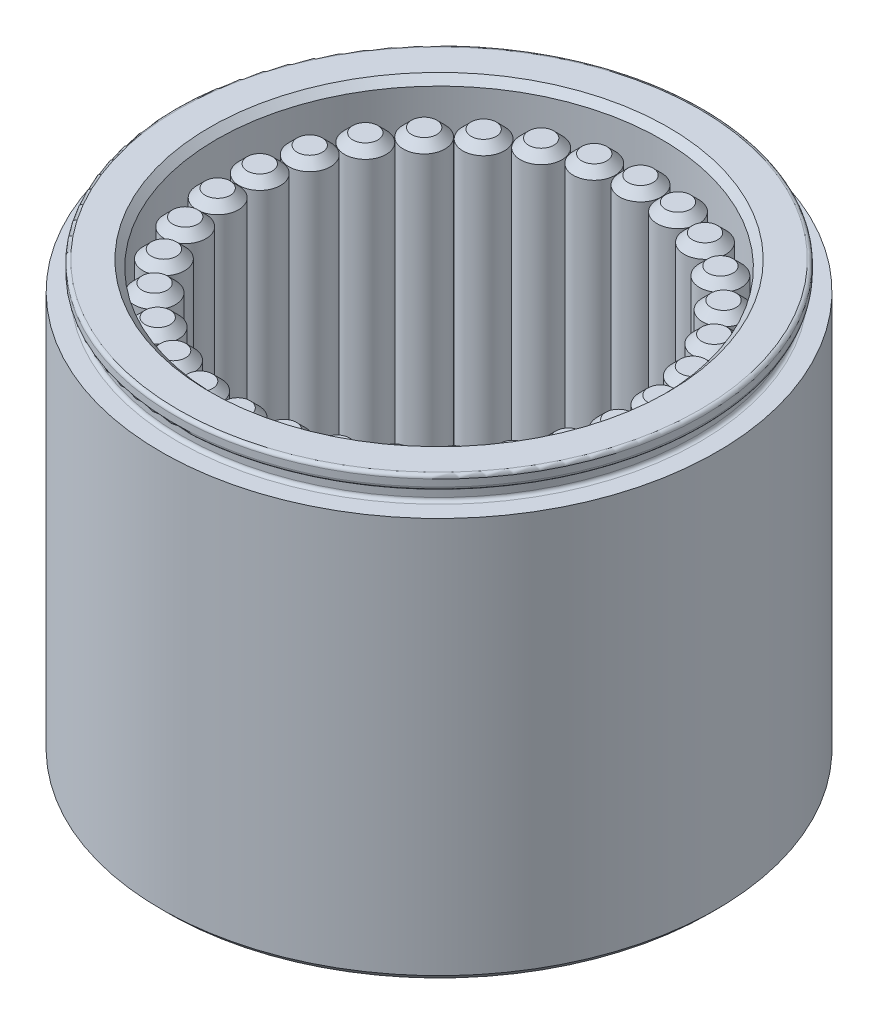
SolidWorks part; units mm, degrees
material "ASTM A36 Acero"
ref_plane "Alzado" through (0, 0, 0) normal (0, 0, 1) x (1, 0, 0)
ref_plane "Planta" through (0, 0, 0) normal (0, 1, 0) x (1, 0, 0)
ref_plane "Vista lateral" through (0, 0, 0) normal (1, 0, 0) x (0, 0, -1)
sketch "Croquis1" plane through (0, 0, 0) normal (0, 0, 1) x (1, 0, 0)
  line L0 (0, 0) -> (20, 0)
  line L1 (20, 0) -> (20, 29)
  line L2 (20, 29) -> (18.5, 29)
  line L3 (18.5, 29) -> (18.5, 30)
  line L4 (18.5, 30) -> (19, 30)
  line L5 (19, 30) -> (19, 31)
  line L6 (19, 31) -> (16, 31)
  line L7 (16, 31) -> (16, 3.7071)
  line L8 (15.2929, 3) -> (13, 3)
  line L9 (13, 3) -> (11.5, 4)
  line L10 (11.5, 4) -> (6, 4)
  line L11 (6, 4) -> (6, 3)
  line L12 (6, 3) -> (0, 3)
  line L13 (0, 3) -> (0, 0) construction
  line L14 (0, 0) -> (0, 3)
  line L15 (15.6464, 2.6464) -> (15.2929, 3)
  line L17 (16, 3.7071) -> (16.3536, 3.3536)
  arc A0 (15.6464, 2.6464) -> (16.3536, 3.3536) centre (16, 3) ccw
  dimension "D9" = 1
  dimension "D1" = 20
  dimension "D2" = 1
  dimension "D3" = 0.5
  dimension "D4" = 3
  dimension "D5" = 4
  dimension "D6" = 26
  dimension "D7" = 3
  dimension "D8" = 4
  dimension "D10" = 4.5
  dimension "D11" = 6
  dimension "D13" = 1.5
revolve "Revolución1" add sketch "Croquis1" angle 360 about L13
chamfer "Chaflán2" distance 0.5 angle 45
fillet "Redondeo3" radius 0.25
sketch "Croquis2" plane through (0, 3, 0) normal (0, 1, 0) x (1, 0, 0)
  circle A0 centre (0, 14.5) radius 1.5
  circle A1 centre (0, 0) radius 16 construction
  circle A2 centre (0, 0) radius 13 construction
extrude "Saliente-Extruir1" add sketch "Croquis2" along normal blind 26 separate body
chamfer "Chaflán1" distance 0.6 angle 45 2 edges at (-1.5, 3, -14.5) (-1.5, 29, -14.5)
pattern_circular "MatrizC1" count 30 over 360 about axis through (0, 0, 0) along (0, 1, 0) of bodies 102
